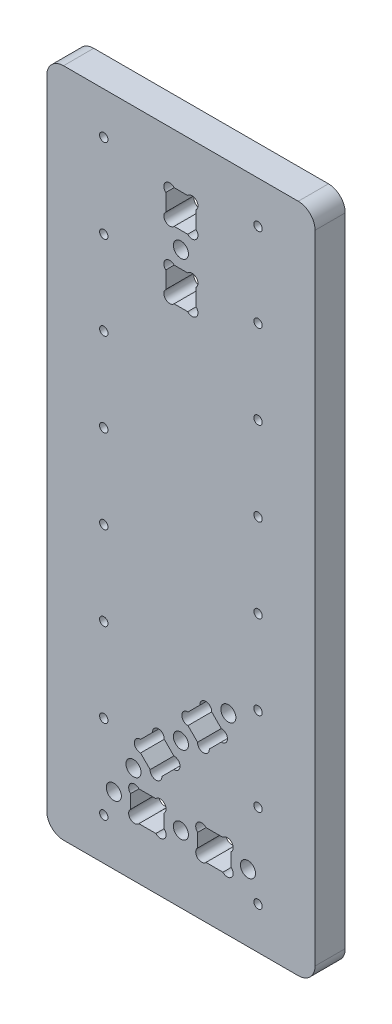
SolidWorks part; units mm, degrees
ref_plane "Plan de face" through (0, 0, 0) normal (0, 0, 1) x (1, 0, 0)
ref_plane "Plan de dessus" through (0, 0, 0) normal (0, 1, 0) x (1, 0, 0)
ref_plane "Plan de droite" through (0, 0, 0) normal (1, 0, 0) x (0, 0, -1)
sketch "Esquisse1" plane through (0, 0, 0) normal (0, 0, 1) x (1, 0, 0)
  line L1 (0, 0) -> (80, 0)
  line L2 (0, 0) -> (0, 200)
  line L3 (0, 200) -> (80, 200)
  line L4 (80, 0) -> (80, 200)
  dimension "D1" = 80
  dimension "D2" = 200
extrude "Boss.-Extru.1" add sketch "Esquisse1" along normal blind 9
sketch "Esquisse2" plane through (0, 0, 9) normal (0, 0, 1) x (1, 0, 0)
  line L0 (40, 0) -> (40, 200) construction
  line L1 (0, 0) -> (80, 0) construction
  line L2 (80, 200) -> (0, 200) construction
  line L3 (17, 0) -> (17, 200) construction
  line L4 (40, 100) -> (0, 100) construction
  line L5 (0, 200) -> (0, 0) construction
  circle A0 centre (17, 187.5) radius 1.25
  circle A1 centre (17, 87.5) radius 1.25
  circle A2 centre (17, 62.5) radius 1.25
  circle A3 centre (17, 37.5) radius 1.25
  circle A4 centre (17, 12.5) radius 1.25
  circle A5 centre (17, 162.5) radius 1.25
  circle A6 centre (17, 137.5) radius 1.25
  circle A7 centre (17, 112.5) radius 1.25
  circle A8 centre (63, 112.5) radius 1.25
  circle A9 centre (63, 137.5) radius 1.25
  circle A10 centre (63, 162.5) radius 1.25
  circle A11 centre (63, 12.5) radius 1.25
  circle A12 centre (63, 37.5) radius 1.25
  circle A13 centre (63, 62.5) radius 1.25
  circle A14 centre (63, 87.5) radius 1.25
  circle A15 centre (63, 187.5) radius 1.25
  dimension "D2" = 2.5
  dimension "D3" = 12.5
  dimension "D4" = 25
  dimension "D5" = 25
  dimension "D1" = 23
  dimension "D6" = 25
extrude "Enlèv. mat.-Extru.1" cut sketch "Esquisse2" against normal through all both and the other way through all
sketch "Esquisse3" plane through (0, 0, 9) normal (0, 0, 1) x (1, 0, 0)
  line L0 (43.182, 0) -> (43.182, 40) construction
  line L2 (43.182, 40) -> (46.7175, 43.5355) construction
  line L3 (46.7175, 43.5355) -> (53.7886, 50.6066)
  line L4 (53.7886, 50.6066) -> (47.4246, 56.9706)
  line L5 (47.4246, 56.9706) -> (40.3536, 49.8995)
  line L6 (40.3536, 49.8995) -> (46.7175, 43.5355)
  line L7 (43.182, 40) -> (32.8481, 50.3339) construction
  line L8 (33.2825, 42.8284) -> (39.6464, 36.4645)
  line L9 (26.2114, 35.7574) -> (33.2825, 42.8284)
  line L10 (32.5754, 29.3934) -> (26.2114, 35.7574)
  line L11 (39.6464, 36.4645) -> (32.5754, 29.3934)
  line L12 (26.2114, 35.7574) -> (17, 35.7574) construction
  line L13 (17, 35.7574) -> (17, 37.5) construction
  line L14 (53.7886, 50.6066) -> (63, 50.6066) construction
  line L15 (63, 50.6066) -> (63, 37.5) construction
  line L16 (0, 0) -> (80, 0) construction
  dimension "D1" = 135
  dimension "D2" = 9
  dimension "D3" = 10
  dimension "D4" = 5
  dimension "D5" = 40
extrude "Enlèv. mat.-Extru.2" cut sketch "Esquisse3" against normal through all both and the other way through all
fillet "Congé1" radius 5 4 edges at (0, 200, 4.5) (80, 200, 4.5) (80, 0, 4.5) (0, 0, 4.5)
sketch "Esquisse4" plane through (0, 0, 9) normal (0, 0, 1) x (1, 0, 0)
  line L0 (32.5754, 29.3934) -> (26.2114, 35.7574) construction
  line L1 (26.2114, 35.7574) -> (33.2825, 42.8284) construction
  line L2 (27.8641, 35.7574) -> (26.2114, 35.7574) construction
  line L3 (27.9614, 37.5074) -> (27.9614, 34.0074)
  line L4 (26.2114, 35.7574) -> (26.1114, 35.7574) construction
  line L5 (29.3934, 32.5754) -> (36.4645, 39.6464) construction
  line L6 (33.2825, 42.8284) -> (39.6464, 36.4645) construction
  line L7 (29.747, 39.2929) -> (36.1109, 32.9289) construction
  line L8 (39.6464, 36.4645) -> (32.5754, 29.3934) construction
  line L9 (33.2825, 42.8284) -> (33.2825, 42.9284) construction
  line L10 (33.2825, 41.1757) -> (33.2825, 42.8284) construction
  line L11 (31.5325, 41.0784) -> (35.0325, 41.0784)
  line L12 (37.9937, 36.4645) -> (39.6464, 36.4645) construction
  line L13 (39.6464, 36.4645) -> (39.7464, 36.4645) construction
  line L14 (32.5754, 29.3934) -> (32.5754, 29.2934) construction
  line L15 (32.5754, 31.0461) -> (32.5754, 29.3934) construction
  line L16 (37.8964, 34.7145) -> (37.8964, 38.2145)
  line L17 (34.3254, 31.1434) -> (30.8254, 31.1434)
  line L18 (36.4645, 39.6464) -> (43.5355, 46.7175) construction
  line L19 (46.7175, 43.5355) -> (40.3536, 49.8995) construction
  line L20 (40, 43.182) -> (36.6519, 46.5301) construction
  line L21 (52.1359, 50.6066) -> (53.7886, 50.6066) construction
  line L22 (53.7886, 50.6066) -> (53.8886, 50.6066) construction
  line L23 (46.7175, 43.5355) -> (46.7175, 43.4355) construction
  line L24 (46.7175, 45.1882) -> (46.7175, 43.5355) construction
  line L25 (42.0063, 49.8995) -> (40.3536, 49.8995) construction
  line L26 (40.3536, 49.8995) -> (40.2536, 49.8995) construction
  line L27 (43.8891, 53.435) -> (50.253, 47.0711) construction
  line L28 (50.6066, 53.7886) -> (43.5355, 46.7175) construction
  line L29 (47.4246, 56.9706) -> (47.4246, 57.0706) construction
  line L30 (47.4246, 55.3179) -> (47.4246, 56.9706) construction
  line L31 (52.0386, 48.8566) -> (52.0386, 52.3566)
  line L32 (48.4675, 45.2855) -> (44.9675, 45.2855)
  line L33 (42.1036, 51.6495) -> (42.1036, 48.1495)
  line L34 (45.6746, 55.2206) -> (49.1746, 55.2206)
  line L35 (29.3934, 32.5754) -> (25.8579, 29.0398) construction
  arc A0 (27.9614, 34.0074) -> (27.9614, 37.5074) centre (27.8641, 35.7574) cw
  arc A1 (35.0325, 41.0784) -> (31.5325, 41.0784) centre (33.2825, 41.1757) ccw
  arc A2 (37.8964, 38.2145) -> (37.8964, 34.7145) centre (37.9937, 36.4645) cw
  arc A3 (30.8254, 31.1434) -> (34.3254, 31.1434) centre (32.5754, 31.0461) ccw
  arc A4 (52.0386, 52.3566) -> (52.0386, 48.8566) centre (52.1359, 50.6066) cw
  arc A5 (44.9675, 45.2855) -> (48.4675, 45.2855) centre (46.7175, 45.1882) ccw
  arc A6 (42.1036, 48.1495) -> (42.1036, 51.6495) centre (42.0063, 49.8995) cw
  arc A7 (49.1746, 55.2206) -> (45.6746, 55.2206) centre (47.4246, 55.3179) ccw
  circle A8 centre (40, 43.182) radius 2.25
  circle A9 centre (25.8579, 29.0398) radius 2.25
  circle A10 centre (54.1421, 57.3241) radius 2.25
  dimension "D2" = 3.5
  dimension "D3" = 5
  dimension "D4" = 4.5
  dimension "D1" = 0.1
extrude "Enlèv. mat.-Extru.3" cut sketch "Esquisse4" against normal through all both and the other way through all
sketch "Esquisse5" plane through (0, 0, 9) normal (0, 0, 1) x (1, 0, 0)
  line L0 (52.0386, 48.8566) -> (48.4675, 45.2855) construction
  line L1 (49.1746, 55.2206) -> (52.0386, 52.3566) construction
  line L2 (42.1036, 51.6495) -> (45.6746, 55.2206) construction
  line L3 (44.9675, 45.2855) -> (42.1036, 48.1495) construction
  line L4 (37.8964, 34.7145) -> (34.3254, 31.1434) construction
  line L5 (35.0325, 41.0784) -> (37.8964, 38.2145) construction
  line L6 (27.9614, 37.5074) -> (31.5325, 41.0784) construction
  line L7 (30.8254, 31.1434) -> (27.9614, 34.0074) construction
  line L8 (52.0386, 48.8566) -> (48.4675, 45.2855) construction
  line L9 (49.1746, 55.2206) -> (52.0386, 52.3566) construction
  line L10 (42.1036, 51.6495) -> (45.6746, 55.2206) construction
  line L11 (44.9675, 45.2855) -> (42.1036, 48.1495) construction
  line L12 (37.8964, 34.7145) -> (34.3254, 31.1434) construction
  line L13 (35.0325, 41.0784) -> (37.8964, 38.2145) construction
  line L14 (27.9614, 37.5074) -> (31.5325, 41.0784) construction
  line L15 (30.8254, 31.1434) -> (27.9614, 34.0074) construction
  line L16 (54.1421, 57.3241) -> (40, 43.182) construction
  line L17 (54.1421, 57.3241) -> (12.0169, 31.591) construction
  line L18 (52.5251, 15.5) -> (47.4749, 15.5)
  line L19 (55, 22.0251) -> (55, 17.9749)
  line L20 (47.4749, 24.5) -> (52.5251, 24.5)
  line L21 (45, 17.9749) -> (45, 22.0251)
  line L22 (32.5251, 15.5) -> (27.4749, 15.5)
  line L23 (35, 22.0251) -> (35, 17.9749)
  line L24 (27.4749, 24.5) -> (32.5251, 24.5)
  line L25 (25, 17.9749) -> (25, 22.0251)
  line L26 (60, 20) -> (40, 20) construction
  line L27 (40, 20) -> (40, 0) construction
  line L28 (44.5, 182.5251) -> (44.5, 177.4749)
  line L29 (5, 0) -> (75, 0) construction
  line L30 (37.9749, 185) -> (42.0251, 185)
  line L31 (35.5, 177.4749) -> (35.5, 182.5251)
  line L32 (42.0251, 175) -> (37.9749, 175)
  line L33 (44.5, 162.5251) -> (44.5, 157.4749)
  line L34 (37.9749, 165) -> (42.0251, 165)
  line L35 (35.5, 157.4749) -> (35.5, 162.5251)
  line L36 (42.0251, 155) -> (37.9749, 155)
  line L37 (40, 190) -> (40, 170) construction
  line L38 (75, 200) -> (5, 200) construction
  circle A0 centre (54.1421, 57.3241) radius 2.25 construction
  arc A1 (52.0386, 48.8566) -> (52.0386, 52.3566) centre (52.1359, 50.6066) ccw construction
  arc A2 (49.1746, 55.2206) -> (45.6746, 55.2206) centre (47.4246, 55.3179) ccw construction
  arc A3 (42.1036, 51.6495) -> (42.1036, 48.1495) centre (42.0063, 49.8995) ccw construction
  arc A4 (44.9675, 45.2855) -> (48.4675, 45.2855) centre (46.7175, 45.1882) ccw construction
  circle A5 centre (40, 43.182) radius 2.25 construction
  circle A6 centre (25.8579, 29.0398) radius 2.25 construction
  arc A7 (30.8254, 31.1434) -> (34.3254, 31.1434) centre (32.5754, 31.0461) ccw construction
  arc A8 (37.8964, 34.7145) -> (37.8964, 38.2145) centre (37.9937, 36.4645) ccw construction
  arc A9 (35.0325, 41.0784) -> (31.5325, 41.0784) centre (33.2825, 41.1757) ccw construction
  arc A10 (27.9614, 37.5074) -> (27.9614, 34.0074) centre (27.8641, 35.7574) ccw construction
  circle A11 centre (54.1421, 57.3241) radius 2.25 construction
  arc A12 (52.0386, 48.8566) -> (52.0386, 52.3566) centre (52.1359, 50.6066) ccw construction
  arc A13 (49.1746, 55.2206) -> (45.6746, 55.2206) centre (47.4246, 55.3179) ccw construction
  arc A14 (42.1036, 51.6495) -> (42.1036, 48.1495) centre (42.0063, 49.8995) ccw construction
  arc A15 (44.9675, 45.2855) -> (48.4675, 45.2855) centre (46.7175, 45.1882) ccw construction
  circle A16 centre (40, 43.182) radius 2.25 construction
  circle A17 centre (25.8579, 29.0398) radius 2.25 construction
  arc A18 (30.8254, 31.1434) -> (34.3254, 31.1434) centre (32.5754, 31.0461) ccw construction
  arc A19 (37.8964, 34.7145) -> (37.8964, 38.2145) centre (37.9937, 36.4645) ccw construction
  arc A20 (35.0325, 41.0784) -> (31.5325, 41.0784) centre (33.2825, 41.1757) ccw construction
  arc A21 (27.9614, 37.5074) -> (27.9614, 34.0074) centre (27.8641, 35.7574) ccw construction
  circle A22 centre (60, 20) radius 2.25
  arc A23 (52.5251, 15.5) -> (55, 17.9749) centre (53.8314, 16.6686) ccw
  arc A24 (55, 22.0251) -> (52.5251, 24.5) centre (53.8314, 23.3314) ccw
  arc A25 (47.4749, 24.5) -> (45, 22.0251) centre (46.1686, 23.3314) ccw
  arc A26 (45, 17.9749) -> (47.4749, 15.5) centre (46.1686, 16.6686) ccw
  circle A27 centre (40, 20) radius 2.25
  circle A28 centre (20, 20) radius 2.25
  arc A29 (25, 17.9749) -> (27.4749, 15.5) centre (26.1686, 16.6686) ccw
  arc A30 (32.5251, 15.5) -> (35, 17.9749) centre (33.8314, 16.6686) ccw
  arc A31 (35, 22.0251) -> (32.5251, 24.5) centre (33.8314, 23.3314) ccw
  arc A32 (27.4749, 24.5) -> (25, 22.0251) centre (26.1686, 23.3314) ccw
  arc A34 (44.5, 182.5251) -> (42.0251, 185) centre (43.3314, 183.8314) ccw
  arc A35 (37.9749, 185) -> (35.5, 182.5251) centre (36.6686, 183.8314) ccw
  arc A36 (35.5, 177.4749) -> (37.9749, 175) centre (36.6686, 176.1686) ccw
  arc A37 (42.0251, 175) -> (44.5, 177.4749) centre (43.3314, 176.1686) ccw
  circle A38 centre (40, 170) radius 2.25
  arc A40 (42.0251, 155) -> (44.5, 157.4749) centre (43.3314, 156.1686) ccw
  arc A41 (44.5, 162.5251) -> (42.0251, 165) centre (43.3314, 163.8314) ccw
  arc A42 (37.9749, 165) -> (35.5, 162.5251) centre (36.6686, 163.8314) ccw
  arc A43 (35.5, 157.4749) -> (37.9749, 155) centre (36.6686, 156.1686) ccw
  circle A44 centre (40, 150) radius 2.25 [skipped]
  circle A45 centre (40, 190) radius 2.25 [skipped]
  point P33 (-95.9274, 30)
  point P66 (12.0169, 31.591)
  point P101 (-35, 95)
  dimension "D1" = 20
  dimension "D3" = 45
  dimension "D5" = 30
  dimension "D2" = 2
  dimension "D4" = 2
extrude "Enlèv. mat.-Extru.4" cut sketch "Esquisse5" against normal through all both and the other way through all
